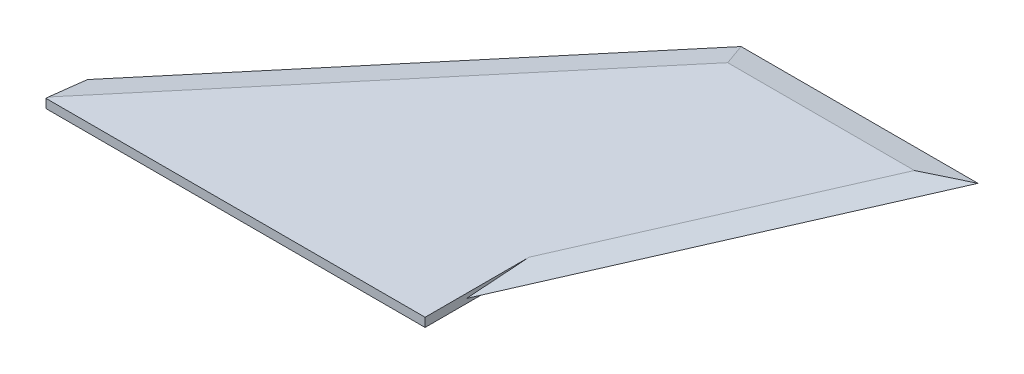
SolidWorks part; units mm, degrees
ref_plane "Front Plane" through (0, 0, 0) normal (0, 0, 1) x (1, 0, 0)
ref_plane "Top Plane" through (0, 0, 0) normal (0, 1, 0) x (1, 0, 0)
ref_plane "Right Plane" through (0, 0, 0) normal (1, 0, 0) x (0, 0, -1)
sketch "Sketch1" plane through (0, 0, 0) normal (0, 1, 0) x (1, 0, 0)
  line L0 (101.6, 0) -> (-101.6, 0) construction
  line L1 (-101.6, 0) -> (58.2485, 190.5)
  line L2 (58.2485, 190.5) -> (185.2485, 190.5)
  line L3 (185.2485, 190.5) -> (101.6, 0)
  line L4 (101.6, -22.225) -> (-101.6, -22.225)
  line L5 (-101.6, -22.225) -> (-101.6, 0)
  line L6 (101.6, 0) -> (101.6, -22.225)
  point P4 (0, 0)
  dimension "D1" = 22.225
  dimension "D2" = 203.2
  dimension "D3" = 127
  dimension "D4" = 190.5
  dimension "D5" = 40
extrude "Boss-Extrude1" add sketch "Sketch1" along normal mid plane 4.7498
chamfer "Chamfer1" distance 2.3749 angle 80 3 edges at (143.4242, 2.3749, -95.25) (-21.6758, 2.3749, -95.25) (121.7485, 2.3749, -190.5) first distance on face at (143.4242, 0, -95.25) first distance on face at (-21.6758, 0, -95.25) first distance on face at (121.7485, 0, -190.5)
chamfer "Chamfer2" distance 2.3749 angle 80 3 edges at (143.4242, -2.3749, -95.25) (-21.6758, -2.3749, -95.25) (121.7485, -2.3749, -190.5) first distance on face at (143.4242, -1.1874, -95.25) first distance on face at (-21.6758, -1.1874, -95.25) first distance on face at (121.7485, -1.1874, -190.5)
equation "\"kerf\"= 0.005"
equation "\"Sweep Angle\" = 40"
equation "\"Tab height\" = 0.875"
equation "\"Tip Chord Length\" = 5"
equation "\"Root Chord Length\" = 8"
equation "\"Height\" = 7.5"
equation "\"D4@Sketch1\"=\"Height\""
equation "\"D3@Sketch1\"=\"Tip Chord Length\""
equation "\"D2@Sketch1\"=\"Root Chord Length\""
equation "\"D1@Sketch1\"=\"Tab height\""
equation "\"D5@Sketch1\"=\"Sweep Angle\""
equation "\"Thicckess\" = 0.187"
equation "\"D1@Boss-Extrude1\"=\"Thicckess\""
